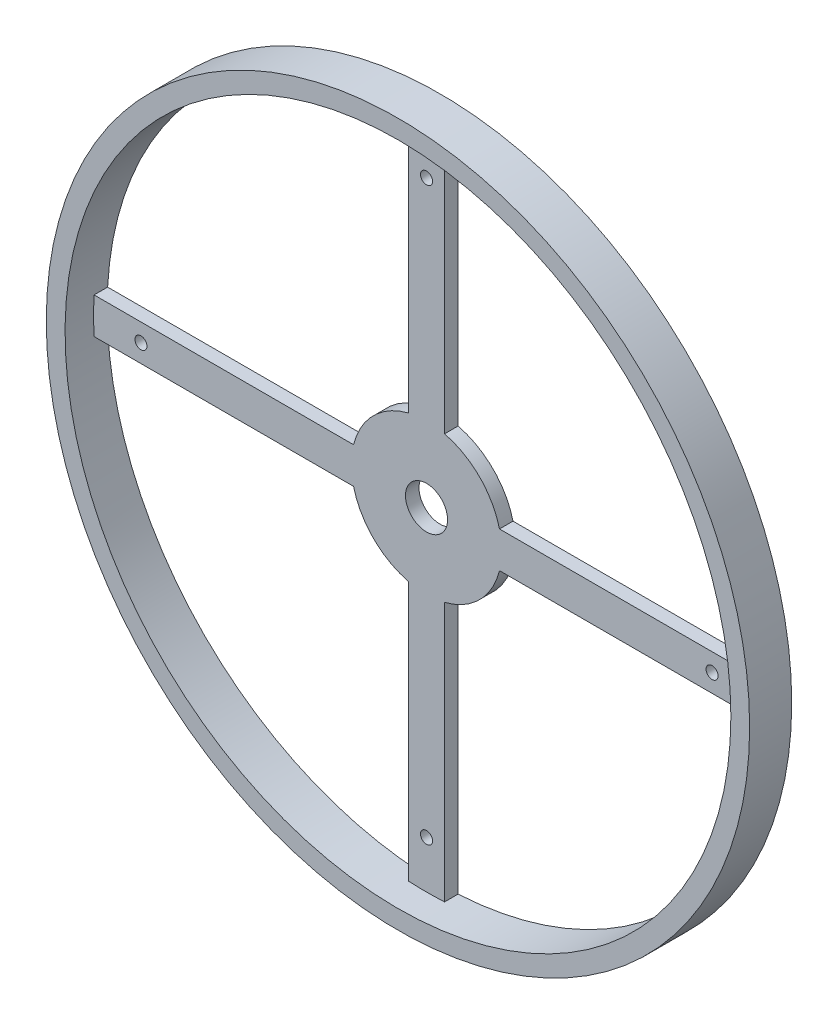
SolidWorks part; units mm, degrees
material "Brass"
ref_plane "Front Plane" through (0, 0, 0) normal (0, 0, 1) x (1, 0, 0)
ref_plane "Top Plane" through (0, 0, 0) normal (0, 1, 0) x (1, 0, 0)
ref_plane "Right Plane" through (0, 0, 0) normal (1, 0, 0) x (0, 0, -1)
sketch "Sketch1" plane through (0, 0, 0) normal (0, 0, 1) x (1, 0, 0)
  line L0 (0, -21.2197) -> (0, 25.1036) construction
  line L1 (-22.3456, 0) -> (19.8849, 0) construction
  line L2 (11.0587, 0.6) -> (2.4269, 0.6)
  line L3 (11.0587, -0.6) -> (2.4269, -0.6)
  line L4 (0.6, 11.0587) -> (0.6, 2.4269)
  line L5 (-0.6, 11.0587) -> (-0.6, 2.4269)
  line L6 (0.6, -11.0587) -> (0.6, -2.4269)
  line L7 (-0.6, -11.0587) -> (-0.6, -2.4269)
  line L8 (-11.0587, -0.6) -> (-2.4269, -0.6)
  line L9 (-11.0587, 0.6) -> (-2.4269, 0.6)
  circle A0 centre (0, 0) radius 0.7
  circle A1 centre (0, 0) radius 2.5
  circle A2 centre (0, 0) radius 11.7
  circle A3 centre (0, 0) radius 11.075
  circle A4 centre (0, -9.5) radius 0.2
  circle A5 centre (-9.5, 0) radius 0.2
  circle A6 centre (0, 9.5) radius 0.2
  circle A7 centre (9.5, 0) radius 0.2
  point P29 (0, 0)
  point P38 (0, 0)
  dimension "D1" = 23.4
  dimension "D2" = 22.15
  dimension "D3" = 5
  dimension "D4" = 1.4
  dimension "D6" = 0.4
  dimension "D5" = 4
  dimension "D7" = 9.5
  dimension "D8" = 4
extrude "Boss-Extrude1" add sketch "Sketch1" along normal blind 1.4 contours A2 A3 region at (-11.3691, 0, 0)
extrude "Boss-Extrude2" add sketch "Sketch1<3>" along normal blind 0.45 contours L4 A3 L5 A1 A6 | L9 A3 L8 A1 A5 | L3 A3 L2 A1 A7 | A1 A0 | L7 A3 L6 A1 A4 region at (6.739, 0, 0) region at (2.4115, 0.2937, 0) region at (0, 6.739, 0) region at (0, -6.739, 0) region at (-6.739, 0, 0)
sketch "Sketch1<3>" plane through (0, 0, 0) normal (0, 0, 1) x (1, 0, 0) same geometry as "Sketch1"
